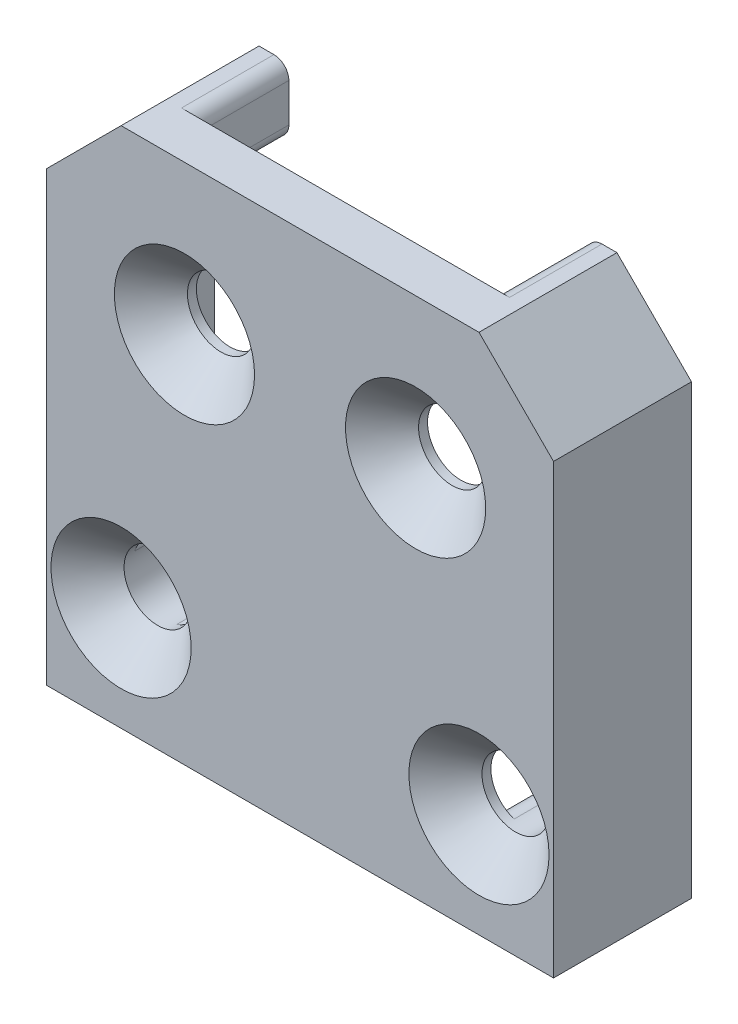
SolidWorks part; units mm, degrees
ref_plane "Спереди" through (0, 0, 0) normal (0, 0, 1) x (1, 0, 0)
ref_plane "Сверху" through (0, 0, 0) normal (0, 1, 0) x (1, 0, 0)
ref_plane "Справа" through (0, 0, 0) normal (1, 0, 0) x (0, 0, -1)
sketch "Sketch1" plane through (0, 0, 0) normal (0, 0, 1) x (1, 0, 0)
  line L6 (3.3574, 30) -> (-20.6426, 30)
  line L7 (-20.6426, 30) -> (-25.6426, 25)
  line L8 (-25.6426, 25) -> (-25.6426, -5)
  line L9 (-25.6426, -5) -> (8.3574, -5)
  line L10 (8.3574, -5) -> (8.3574, 25)
  line L11 (8.3574, 25) -> (3.3574, 30)
  line L12 (3.3574, 30) -> (-20.6426, 30)
  line L13 (-20.6426, 30) -> (-25.6426, 25)
  line L14 (-25.6426, 25) -> (-25.6426, -5)
  line L15 (-25.6426, -5) -> (8.3574, -5)
  line L16 (8.3574, -5) -> (8.3574, 25)
  line L17 (8.3574, 25) -> (3.3574, 30)
  dimension "D1" = 0
extrude "Extrude1" add sketch "Sketch1" along normal offset from surface (9.25 mm away) 0.25
hole_wizard "CSK for M4 Countersunk Raised Head Screw1" positions "Sketch4" profile "Sketch5" countersink size "M4" standard "ISO" end condition up to next
sketch "Sketch4" plane through (0, 0, 9.25) normal (0, 0, 1) x (1, 0, 0)
  point P0 (-0.8926, 20)
  point P2 (-16.3926, 20)
  point P4 (-20.6426, 2)
  point P6 (3.3574, 2)
  point P9 (3.3574, 2)
  point P11 (-20.6426, 2)
  point P13 (-16.3926, 20)
  point P15 (-0.8926, 20)
sketch "Sketch5" plane through (-0.8926, 20, 9.25) normal (1, 0, 0) x (0, -1, 0)
  line L0 (0, 0) -> (0, 9.25)
  line L1 (0, 9.25) -> (2.25, 9.25)
  line L2 (2.25, 9.25) -> (2.25, 2.45)
  line L3 (2.25, 2.45) -> (4.7, 0)
  line L5 (4.7, 0) -> (0, 0)
  line L6 (-2.25, 2.45) -> (-4.7, 0) construction
  line L11 (0, -6.35) -> (0, 107.95) construction
  dimension "Диаметр сквозного отверстия" = 4.5
  dimension "Глубина сквозного отверстия" = 9.25
  dimension "Диаметр передней зенковки" = 9.4
  dimension "Угол передней зенковки" = 90
sketch "Sketch6" plane through (0, 0, 0) normal (0, 0, -1) x (-1, 0, 0)
  line L0 (-1.3574, -5) -> (-1.3574, 2)
  line L1 (25.6426, -5) -> (-8.3574, -5) construction
  line L2 (-3.3574, 4) -> (-6.3574, 4)
  line L3 (-6.3574, 4) -> (-6.3574, 21)
  line L4 (-6.3574, 21) -> (-1.3574, 26)
  line L5 (-1.3574, 26) -> (-1.3574, 30)
  line L6 (-3.3574, 30) -> (20.6426, 30) construction
  line L7 (-1.3574, 30) -> (18.6426, 30)
  line L8 (18.6426, 30) -> (18.6426, 26)
  line L9 (18.6426, 26) -> (23.6426, 21)
  line L10 (23.6426, 21) -> (23.6426, 4)
  line L11 (23.6426, 4) -> (20.6426, 4)
  line L12 (18.6426, 2) -> (18.6426, -5)
  line L13 (18.6426, -5) -> (-1.3574, -5)
  line L14 (8.6426, -5) -> (8.6426, 30) construction
  arc A0 (20.6426, 4) -> (18.6426, 2) centre (20.6426, 2) ccw
  arc A1 (-1.3574, 2) -> (-3.3574, 4) centre (-3.3574, 2) ccw
  point P19 (0.8926, 20)
  dimension "D3" = 2
  dimension "D1" = 20
  dimension "D2" = 16
  dimension "D4" = 30
  dimension "D5" = 22
  dimension "D6" = 20
extrude "Extrude2" cut sketch "Sketch6" against normal blind 6.2
fillet "Fillet1" radius 1 10 edges at (1.3574, -5, 3.1) (-18.6426, -5, 3.1) (-18.6426, 30, 3.1) (1.3574, 30, 3.1) (1.3574, 26, 3.1) (-18.6426, 26, 3.1) (4.3882, 4, 3.1) (1.3574, 0.9692, 3.1) (-18.6426, 0.9692, 3.1) (-21.6734, 4, 3.1)
fillet "Fillet2" radius 1 2 edges at (6.3574, 4, 3.1) (-23.6426, 4, 3.1)
fillet "Fillet3" radius 5 2 edges at (6.3574, 21, 3.1) (-23.6426, 21, 3.1)
